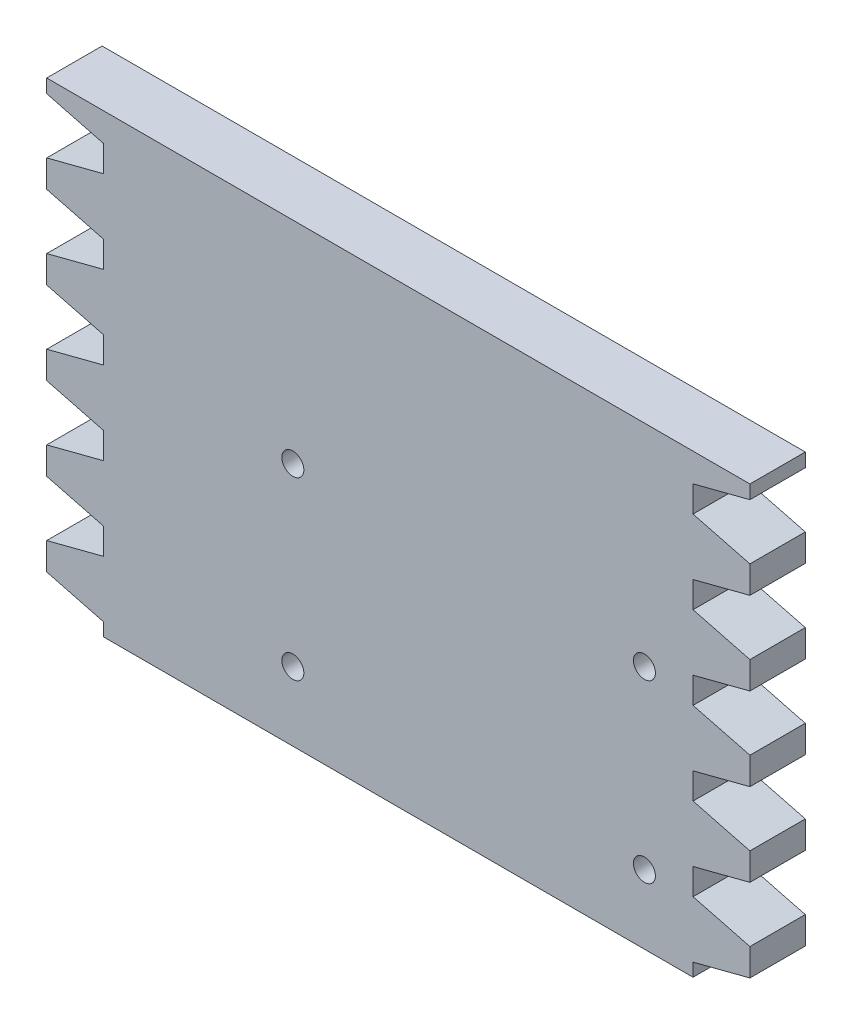
SolidWorks part; units mm, degrees
ref_plane "Front Plane" through (0, 0, 0) normal (0, 0, 1) x (1, 0, 0)
ref_plane "Top Plane" through (0, 0, 0) normal (0, 1, 0) x (1, 0, 0)
ref_plane "Right Plane" through (0, 0, 0) normal (1, 0, 0) x (0, 0, -1)
sketch "Sketch1" plane through (0, 0, 0) normal (0, 0, 1) x (1, 0, 0)
  line L0 (-19.05, 32.9161) -> (31.75, 32.9161)
  line L1 (31.75, 31.9317) -> (31.75, 32.9161)
  line L2 (27.6409, 30.869) -> (31.75, 31.9317)
  line L3 (6.35, 32.9161) -> (6.35, 0) construction
  line L4 (27.6409, 0) -> (-14.9409, 0)
  line L5 (-14.9409, 0) -> (-14.9409, 0.9453)
  line L6 (-14.9409, 0.9453) -> (-19.05, 2.008)
  line L7 (27.6409, 28.9784) -> (27.6409, 30.869)
  line L8 (-19.05, 2.008) -> (-19.05, 3.9768)
  line L9 (-19.05, 3.9768) -> (-14.9409, 5.0394)
  line L10 (-14.9409, 5.0394) -> (-14.9409, 6.9301)
  line L11 (-14.9409, 6.9301) -> (-19.05, 7.9927)
  line L12 (-19.05, 7.9927) -> (-19.05, 9.9615)
  line L13 (-19.05, 9.9615) -> (-14.9409, 11.0242)
  line L14 (-14.9409, 11.0242) -> (-14.9409, 12.9148)
  line L15 (-14.9409, 12.9148) -> (-19.05, 13.9775)
  line L16 (-19.05, 13.9775) -> (-19.05, 15.9463)
  line L17 (-19.05, 15.9463) -> (-14.9409, 17.0089)
  line L18 (-14.9409, 17.0089) -> (-14.9409, 18.8996)
  line L19 (31.75, 27.9158) -> (27.6409, 28.9784)
  line L20 (31.75, 25.947) -> (31.75, 27.9158)
  line L21 (-14.9409, 18.8996) -> (-19.05, 19.9622)
  line L22 (-19.05, 19.9622) -> (-19.05, 21.931)
  line L23 (-19.05, 21.931) -> (-14.9409, 22.9937)
  line L24 (-14.9409, 22.9937) -> (-14.9409, 24.8843)
  line L25 (-14.9409, 24.8843) -> (-19.05, 25.947)
  line L26 (-19.05, 25.947) -> (-19.05, 27.9158)
  line L27 (-19.05, 27.9158) -> (-14.9409, 28.9784)
  line L28 (-14.9409, 28.9784) -> (-14.9409, 30.869)
  line L29 (-14.9409, 30.869) -> (-19.05, 31.9317)
  line L30 (-19.05, 31.9317) -> (-19.05, 32.9161)
  line L31 (27.6409, 24.8843) -> (31.75, 25.947)
  line L32 (27.6409, 22.9937) -> (27.6409, 24.8843)
  line L33 (31.75, 21.931) -> (27.6409, 22.9937)
  line L34 (31.75, 19.9622) -> (31.75, 21.931)
  line L35 (27.6409, 18.8996) -> (31.75, 19.9622)
  line L36 (27.6409, 17.0089) -> (27.6409, 18.8996)
  line L37 (31.75, 15.9463) -> (27.6409, 17.0089)
  line L38 (31.75, 13.9775) -> (31.75, 15.9463)
  line L39 (27.6409, 12.9148) -> (31.75, 13.9775)
  line L40 (27.6409, 11.0242) -> (27.6409, 12.9148)
  line L41 (31.75, 9.9615) -> (27.6409, 11.0242)
  line L42 (31.75, 7.9927) -> (31.75, 9.9615)
  line L43 (27.6409, 6.9301) -> (31.75, 7.9927)
  line L44 (27.6409, 5.0394) -> (27.6409, 6.9301)
  line L45 (31.75, 3.9768) -> (27.6409, 5.0394)
  line L46 (31.75, 2.008) -> (31.75, 3.9768)
  line L47 (27.6409, 0.9453) -> (31.75, 2.008)
  line L48 (27.6409, 0) -> (27.6409, 0.9453)
  dimension "D1" = 25.4
  dimension "D2" = 32.9161
extrude "Boss-Extrude1" add sketch "Sketch1" along normal blind 4 contours L0 L1 L2 L7 L19 L20 L31 L32 L33 L34 L35 L36 L37 L38 L39 L40 L41 L42 L43 L44 L45 L46 L47 L48 L4 L5 L6 L8 L9 L10 L11 L12 L13 L14 L15 L16 L17 L18 L21 L22 L23 L24 L25 L26 L27 L28 L29 L30
sketch "Sketch2" plane through (0, 0, 4) normal (0, 0, 1) x (1, 0, 0)
  line L0 (-19.05, 32.9161) -> (31.75, 32.9161) construction
  circle A0 centre (-1.27, 17.6761) radius 0.7937
  circle A1 centre (24.13, 17.6761) radius 0.7937
  circle A2 centre (24.13, 4.9761) radius 0.7937
  circle A3 centre (-1.27, 4.9761) radius 0.7938
  point P4 (6.35, 32.9161)
  point P5 (0, 0)
  dimension "D3" = 1.5875
  dimension "D1" = 15.24
  dimension "D2" = 7.62
  dimension "D6" = 12.7
  dimension "D4" = 2
  dimension "D5" = 2
extrude "Cut-Extrude1" cut sketch "Sketch2" against normal blind 4
